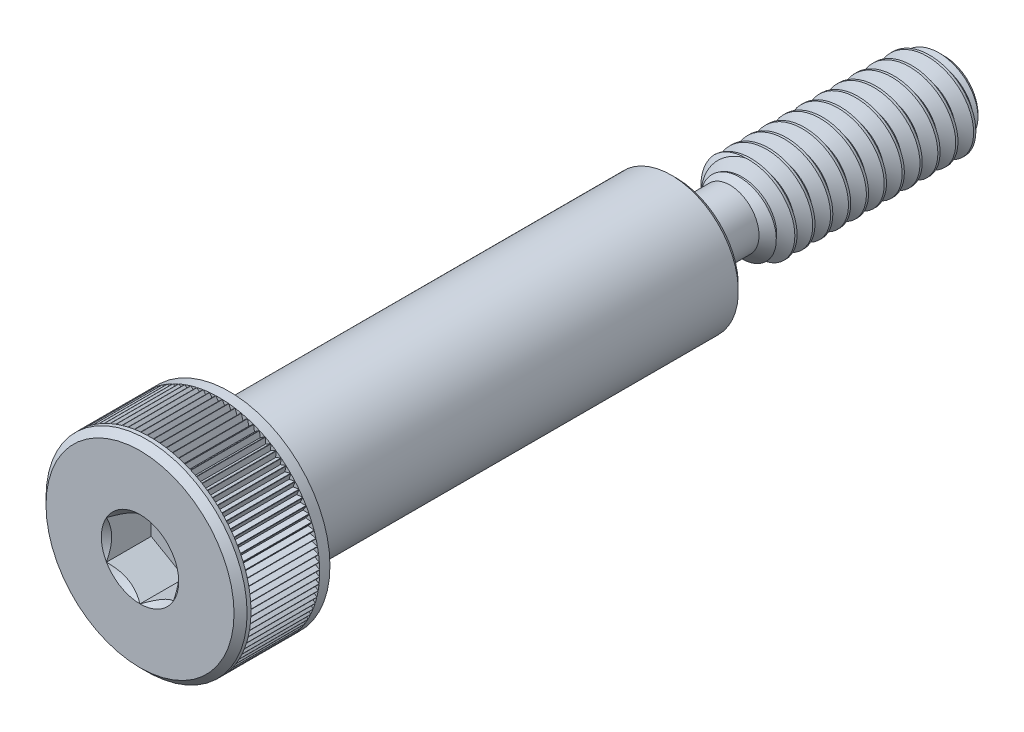
SolidWorks part; units mm, degrees
note: '?' marks a value the reader was unsure of.
other "DetailItem1"
other "DetailItem2"
other "DetailItem5"
other "DetailItem6"
ref_plane "Front" through (0, 0, 0) normal (0, 0, 1) x (1, 0, 0)
ref_plane "Top" through (0, 0, 0) normal (0, 1, 0) x (1, 0, 0)
ref_plane "Right" through (0, 0, 0) normal (1, 0, 0) x (0, 0, -1)
sketch "Sketch1" plane through (0, 0, 0) normal (1, 0, 0) x (0, 0, -1)
  line L0 (0, 7.1437) -> (6.35, 7.1437) construction
  line L1 (6.35, 7.1437) -> (6.35, 4.4053) construction
  line L2 (7.9772, 4.7625) -> (38.1, 4.7625) construction
  line L3 (7.9772, -4.7625) -> (38.1, -4.7625) construction
  line L4 (38.1, 3.175) -> (57.15, 3.175) construction
  line L5 (57.15, 3.175) -> (57.15, 0) construction
  line L6 (38.1, 0) -> (0, 0) construction
  line L7 (0, 0) -> (0, 7.1437) construction
  line L8 (0, 7.1437) -> (0, -7.1438) construction
  line L9 (57.15, 3.175) -> (57.15, -3.175) construction
  line L10 (38.1, 4.7625) -> (38.1, -4.7625) construction
  line L11 (57.15, -3.175) -> (55.4722, -3.175) construction
  line L12 (38.1, 4.7625) -> (38.1, 0) construction
  line L13 (6.35, 4.4053) -> (7.62, 4.4053) construction
  line L14 (7.62, 4.4053) -> (7.9772, 4.7625) construction
  line L15 (57.15, 0) -> (38.1, 0) construction
  line L16 (7.62, -4.4053) -> (7.9772, -4.7625) construction
  line L17 (6.35, -4.4053) -> (7.62, -4.4053) construction
  line L18 (0, -7.1438) -> (6.35, -7.1438) construction
  line L19 (6.35, -7.1438) -> (6.35, -4.4053) construction
  line L20 (57.15, 4.7625) -> (55.245, 4.7625) construction
  line L21 (57.15, -4.7625) -> (55.245, -4.7625) construction
  line L22 (57.15, 0) -> (76.2, 0) construction
  line L23 (22.225, 0) -> (22.225, 7.1438) construction
  line L24 (57.15, -4.7625) -> (57.15, 4.7625) construction
  line L25 (0, -2.3813) -> (0, 2.3813) construction
  line L26 (57.0706, 3.3125) -> (58.3406, 3.3125) construction
  line L27 (58.3406, 3.3125) -> (57.7056, 2.2126) construction
  line L28 (57.7056, 2.2126) -> (57.0706, 3.3125) construction
  line L29 (57.7056, 2.2126) -> (57.7056, 2.3501) construction
  line L30 (57.7056, 3.3125) -> (57.7056, 3.175) construction
  line L31 (58.2613, 3.175) -> (57.15, 3.175) construction
  line L32 (57.6263, 2.3501) -> (57.785, 2.3501) construction
  line L33 (57.7056, 3.2437) -> (58.3009, 3.2437) construction
  line L34 (57.7056, 3.2437) -> (57.1103, 3.2437) construction
  line L35 (7.9772, 4.7625) -> (7.9772, -4.7625) construction
  line L36 (37.7428, 4.7625) -> (38.1, 4.4053) construction
  line L37 (37.7428, 4.7625) -> (37.7428, 0) construction
  point P2 (7.1438, 0)
  point P8 (55.245, -3.175)
  point P12 (38.1, 0)
  point P15 (37.3063, 0)
  point P31 (8.6519, 0)
  point P32 (35.7981, 0)
  point P34 (57.15, 0)
  point P37 (0, 0)
  dimension "D1" = 1.905
  dimension "D2" = 1.6778
  dimension "D3" = 135
  dimension "D4" = 1.27
  dimension "D5" = 0.3572
  dimension "D6" = 15.875
  dimension "D7" = 30.1625
  dimension "D8" = 27.1463
  dimension "D9" = 0.1588
  dimension "Shoulder Lg" = 31.75
  dimension "D10" = 45
sketch "Sketch13" plane through (0, 0, 0) normal (1, 0, 0) x (0, 0, -1)
  line L0 (0, 0) -> (0, 7.1437)
  line L1 (0, 7.1437) -> (6.35, 7.1437)
  line L2 (6.35, 7.1437) -> (6.35, 4.4053)
  line L3 (6.35, 4.4053) -> (7.62, 4.4053)
  line L4 (38.1, 0) -> (38.1, 4.4053)
  line L5 (7.62, 4.4053) -> (7.9772, 4.7625)
  line L7 (38.1, 4.7625) -> (38.1, 0) construction
  line L8 (38.1, 4.7625) -> (38.1, -4.7625) construction
  line L9 (38.1, 0) -> (0, 0) construction
  line L10 (38.1, 4.4053) -> (37.7428, 4.7625)
  line L12 (7.9772, 4.7625) -> (37.7428, 4.7625)
  line L13 (0, 0) -> (38.1, 0)
  line L14 (7.9772, 4.7625) -> (38.1, 4.7625) construction
  line L18 (57.15, 4.7625) -> (57.15, -4.7625) construction
  dimension "D1" = 31.75
  dimension "D2" = 45
  dimension "D3" = 9.525
revolve "Revolve1" add sketch "Sketch13" angle 360 about L9
sketch "Sketch12" plane through (0, 0, -38.1) normal (0, 0, -1) x (-1, 0, 0)
  circle A0 centre (0, 0) radius 3.175
extrude "Boss-Extrude1" add sketch "Sketch12" along normal up to vertex (19.05 mm away) up to point (0, 0, -57.15)
ref_plane "Plane1" through (0, 0, -57.15) normal (0, 0, 1) x (1, 0, 0)
sketch "Sketch3" plane through (0, 0, -57.15) normal (0, 0, 1) x (1, 0, 0)
  circle A0 centre (0, 0) radius 3.175
sketch "Sketch5" plane through (0, 0, 0) normal (1, 0, 0) x (0, 0, -1)
  line L0 (38.1, 3.175) -> (43.0213, 3.175)
  line L1 (43.0213, 3.175) -> (41.91, 2.0638)
  line L2 (41.91, 2.0638) -> (38.1, 2.0637)
  line L3 (38.1, 3.175) -> (38.1, 2.0637)
  line L4 (38.1, 3.175) -> (57.15, 3.175) construction
  line L5 (38.1, 4.7625) -> (38.1, 0) construction
  line L6 (38.1, 4.7625) -> (38.1, -4.7625) construction
  line L7 (57.15, 0) -> (38.1, 0) construction
  line L8 (57.15, -3.175) -> (57.15, 3.175) construction
  dimension "D4" = 3.81
  dimension "D1" = 45
  dimension "D2" = 15.24
  dimension "D3" = 2.0638
revolve "Cut-Revolve1" cut sketch "Sketch5" angle 360 mid plane about L6
chamfer "Chamfer1" distance 0.7937 angle 45 1 edges at (-3.175, 0, -57.15)
chamfer "Chamfer2" distance 0.4643 angle 45 1 edges at (-7.1437, 0, 0)
fillet "Fillet1" radius 0.3175 1 edges at (0, 2.0637, -38.1)
sketch "Sketch10" plane through (0, 0, 0) normal (1, 0, 0) x (0, 0, -1)
  line L0 (0.4643, 0) -> (5.8857, 0) construction
  line L1 (6.35, -7.1437) -> (6.35, 7.1437) construction
  line L2 (0.4643, -7.1437) -> (0.4643, 7.1437) construction
  line L3 (0.4643, 0) -> (0, 0) construction
  line L4 (5.8857, 0) -> (6.35, 0) construction
  point P6 (3.175, 0)
  dimension "D1" = 5.4213
ref_plane "Plane2" through (0, 0, -3.175) normal (0, 0, 1) x (1, 0, 0)
sketch "Sketch8" plane through (0, 0, 0) normal (0, 0, 1) x (1, 0, 0)
  line L1 (2.3812, 1.3748) -> (0, 2.7496)
  line L2 (0, 2.7496) -> (-2.3813, 1.3748)
  line L3 (-2.3813, 1.3748) -> (-2.3813, -1.3748)
  line L4 (-2.3813, -1.3748) -> (0, -2.7496)
  line L5 (0, -2.7496) -> (2.3812, -1.3748)
  line L6 (2.3812, -1.3748) -> (2.3812, 1.3748)
  circle A0 centre (0, 0) radius 2.3813 construction
extrude "Cut-Extrude2" cut sketch "Sketch8" against normal blind 3.175
sketch "Sketch9" plane through (0, 0, 0) normal (0, 0, 1) x (1, 0, 0)
  circle A0 centre (0, 0) radius 2.7496
extrude "Cut-Extrude4" cut sketch "Sketch9" against normal blind 3.175 draft 45
sketch "Sketch16" plane through (0, 0, 0) normal (0, 1, 0) x (1, 0, 0)
  line L0 (0, 22.225) -> (-4.7625, 22.225) construction
  line L1 (-4.7625, 37.7428) -> (-4.7625, 7.9772) construction
  line L2 (0, 35.7981) -> (-4.7625, 35.7981) construction
  line L3 (0, 22.225) -> (0, 35.7981) construction
  line L4 (0, 29.0116) -> (0, 35.7981) construction
  line L5 (0, 35.7981) -> (0, 32.4048) construction
  line L6 (0, 32.4048) -> (-4.7625, 32.4048) construction
  line L7 (0, 7.9772) -> (-4.7625, 7.9772) construction
  line L8 (-4.7625, 7.9772) -> (4.7625, 7.9772) construction
  line L9 (0, 38.1) -> (4.7625, 38.1) construction
  point P0 (0, 22.225)
  point P2 (0, 35.7981)
  point P11 (0, 7.9772)
sketch "reference 1" plane through (0, 0, -6.35) normal (0, 0, -1) x (-1, 0, 0)
  circle A1 centre (0, 0) radius 7.1437
ref_axis "Center Axis 1" through (0, 0, -7.9772) along (0, 0, -1)?
ref_plane "Contact Plane 1" through (0, 0, -57.15) normal (0, 0, -1) x (-1, 0, 0)
ref_plane "Contact Plane 2" through (0, 0, -6.35) normal (0, 0, -1) x (-1, 0, 0)
ref_plane "Plane3" through (0, 0, -38.1) normal (0, 0, 1) x (1, 0, 0)
split "Split1" trim tools "Plane3" bodies to split 118 resulting bodies 127 128
sketch "Sketch15" plane through (0, 0, -57.15) normal (0, 0, -1) x (-1, 0, 0)
  circle A0 centre (0, 0) radius 3.175
curve "Helix/Spiral1" pitch 1.27 height 17.78 radius 3.175 centre (0, 0, -57.15) axis (0, 0, 1) start towards (0, 1, 0)
sketch "Sketch4" plane through (0, 0, 0) normal (1, 0, 0) x (0, 0, -1)
  line L0 (57.6263, 2.3501) -> (57.785, 2.3501) construction
  line L1 (58.3406, 3.3125) -> (57.7056, 2.2126) construction
  line L3 (57.7056, 3.2437) -> (58.3009, 3.2437) construction
  line L4 (57.7056, 3.2437) -> (57.1103, 3.2437) construction
  line L5 (57.7056, 2.2126) -> (57.0706, 3.3125) construction
  line L6 (57.6263, 2.3501) -> (57.785, 2.3501)
  line L7 (58.3009, 3.2437) -> (57.785, 2.3501)
  line L8 (57.7056, 3.2437) -> (58.3009, 3.2437)
  line L9 (57.7056, 3.2437) -> (57.1103, 3.2437)
  line L10 (57.6263, 2.3501) -> (57.1103, 3.2437)
sweep "Cut-Sweep1" cut profiles "Sketch4" path "Helix/Spiral1" align with end faces yes
sketch "Sketch14" plane through (0, 0, -38.1) normal (0, 0, -1) x (-1, 0, 0)
  line L0 (0, -4.7625) -> (0, 4.7625) construction
  circle A0 centre (0, 0) radius 1.5875
  dimension "D1" = 3.175
extrude "Boss-Extrude2" add sketch "Sketch14" along normal up to vertex (17.145 mm away) up to point (0, 4.7625, -55.245)
sketch "Sketch11" plane through (0, 0, -3.175) normal (0, 0, 1) x (1, 0, 0)
  line L0 (0, 6.7723) -> (0, 7.1437) construction
  line L1 (0, 6.7723) -> (0.2145, 7.1437)
  line L2 (0, 6.7723) -> (-0.2145, 7.1437)
  line L3 (-0.2145, 7.1437) -> (0.2145, 7.1437)
  line L4 (0, 0) -> (-0.2145, 7.1437) construction
  line L5 (0.2145, 7.1437) -> (0, 0) construction
  circle A2 centre (0, 0) radius 7.1437 construction
  point P8 (2.3908, 0.7309)
  dimension "D1" = 0.3715
  dimension "D2" = 3.439
extrude "Cut-Extrude5" cut sketch "Sketch11" along normal blind 2.4396 and the other way blind 2.4396
pattern_circular "CirPattern1" count 99 over 360 about axis through (0, 0, 0) along (0, 0, 1) of "Cut-Extrude5"
equation "\"D1@Chamfer1\" = \"Thread Dia@Sketch1\" * .125"
equation "\"D1@Cut-Extrude2\"= \"Head Ht@Sketch1\" * .5"
equation "\"D1@Cut-Extrude4\" = \"D1@Cut-Extrude2\""
equation "\"D1@Chamfer2\"=\"Head Dia@Sketch1\" * .0325"
equation "\"D1@Sketch1\"=\"Pitch@Sketch1\"*1.5"
equation "\"D1@Sketch11\"=\"D1@Chamfer2\"*.8"
equation "\"D4@Sketch5\"=\"Thread Lg@Sketch1\"*0.2"
equation "\"D3@Sketch5\"=(\"Thread Dia@Sketch1\"*0.65)/2"
equation "\"D1@Fillet1\"=\"Pitch@Sketch1\"*.25"
equation "\"D1@Cut-Extrude5\"=\"D1@Sketch10\"*.45"
equation "\"D1@CirPattern1\"=(360/(\"D2@Sketch11\"))-6"
equation "\"D4@Sketch1\"=\"Head Ht@Sketch1\"*0.2"
equation "\"D5@Sketch1\"=\"Head Dia@Sketch1\"*0.025"
equation "\"D6@Sketch1\"=\"Shoulder Lg@Sketch1\"/2"
equation "\"D7@Sketch1\"=\"Shoulder Lg@Sketch1\"*0.95"
equation "\"D8@Sketch1\"=\"D7@Sketch1\"*0.9"
equation "\"D2@Cut-Extrude5\"=\"D1@Sketch10\"*.45"
equation "\"D9@Sketch1\"=\"Pitch@Sketch1\"/8"
equation "\"D1@Sketch14\"=\"Thread Dia@Sketch1\"*.5"
equation "\"D4@Helix/Spiral1\"=\"Pitch@Sketch1\""
equation "\"D3@Helix/Spiral1\"=\"Thread Lg@Sketch1\"-\"Pitch@Sketch1\""
